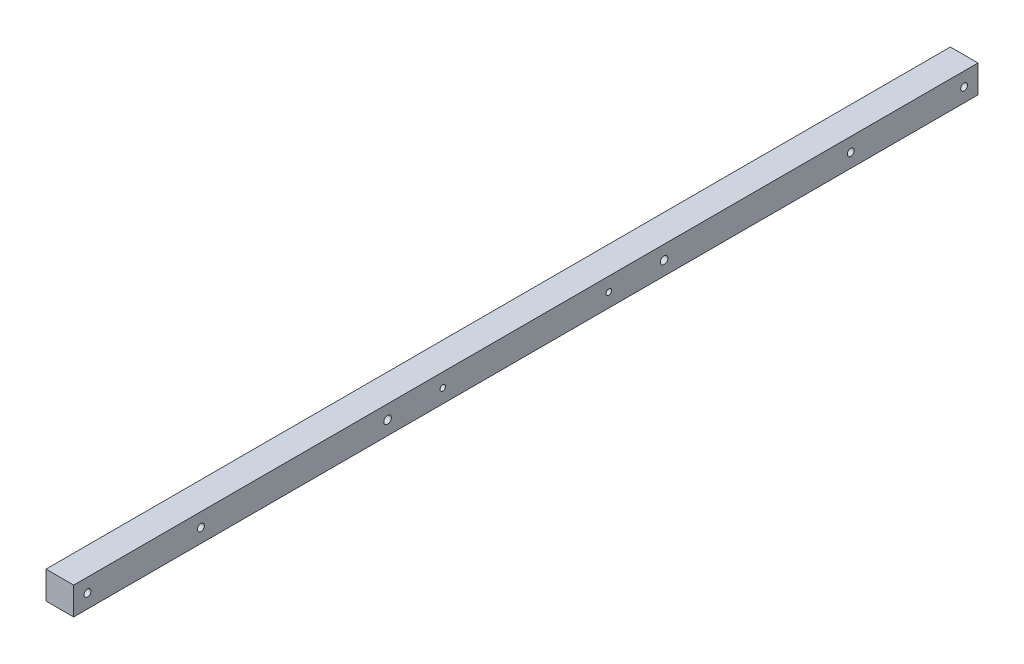
SolidWorks part; units mm, degrees
ref_plane "Front Plane" through (0, 0, 0) normal (0, 0, 1) x (1, 0, 0)
ref_plane "Top Plane" through (0, 0, 0) normal (0, 1, 0) x (1, 0, 0)
ref_plane "Right Plane" through (0, 0, 0) normal (1, 0, 0) x (0, 0, -1)
sketch "Sketch1" plane through (0, 0, 0) normal (0, 0, 1) x (1, 0, 0)
  line L5 (-12.7, -12.7) -> (12.7, -12.7)
  line L6 (-12.7, -12.7) -> (-12.7, 12.7)
  line L7 (-12.7, 12.7) -> (12.7, 12.7)
  line L8 (12.7, -12.7) -> (12.7, 12.7)
  line L9 (-12.7, -12.7) -> (12.7, 12.7) construction
  line L10 (-12.7, 12.7) -> (12.7, -12.7) construction
  point P0 (0, 0)
  dimension "D1" = 25.4
  dimension "D2" = 25.4
extrude "Boss-Extrude1" add sketch "Sketch1" along normal blind 830.58
sketch "Sketch2" plane through (-12.7, 0, 0) normal (1, 0, 0) x (0, 0, -1)
  line L0 (0, 0) -> (-830.58, 0) construction
  line L2 (0, 12.7) -> (0, -12.7) construction
  line L4 (0, -12.7) -> (0, 12.7) construction
  line L5 (-830.58, 12.7) -> (-830.58, -12.7) construction
  circle A0 centre (-12.7, 0) radius 3.175
  circle A2 centre (-116.84, 0) radius 3.175
  circle A4 centre (-288.29, 0) radius 3.5
  point P15 (-415.29, 0)
  dimension "D1" = 6.35
  dimension "D2" = 12.7
  dimension "D5" = 7
  dimension "D3" = 104.14
  dimension "D4" = 127
ref_plane "Plane1" through (0, 0, 415.29) normal (0, 0, -1) x (-1, 0, 0)
extrude "Cut-Extrude4" cut sketch "Sketch2" along normal through all
mirror "Mirror1" about plane through (0, 0, 415.29) normal (0, 0, -1) of "Cut-Extrude4"
hole_wizard "1/4-20 Tapped Hole1" positions "Sketch4" profile "Sketch6" tap size "1/4-20" standard "ANSI Inch"
sketch "Sketch4" plane through (12.7, 0, 0) normal (1, 0, 0) x (0, 0, -1)
  line L2 (-339.09, 0) -> (-491.49, 0) construction
  line L4 (-415.29, 12.7) -> (-415.29, 0) construction
  line L6 (-830.58, 12.7) -> (0, 12.7) construction
  line L7 (-339.09, 0) -> (0, 0) construction
  point P0 (-339.09, 0)
  point P2 (-491.49, 0)
  dimension "D1" = 152.4
sketch "Sketch6" plane through (12.7, 0, 339.09) normal (0, 1, 0) x (0, 0, -1)
  line L0 (0, 0) -> (0, 20.5838)
  line L1 (0, 20.5838) -> (2.5527, 19.05)
  line L2 (2.5527, 19.05) -> (2.5527, 0)
  line L5 (2.5527, 0) -> (0, 0)
  line L10 (0, 20.5838) -> (-2.5527, 19.05) construction
  line L11 (0, -6.35) -> (0, 107.95) construction
  dimension "Tap Drill Dia." = 5.1054
  dimension "Tap Drill Depth" = 19.05
  dimension "Drill Angle" = 118
cosmetic thread "Hole Thread1"
cosmetic thread "Hole Thread2"
